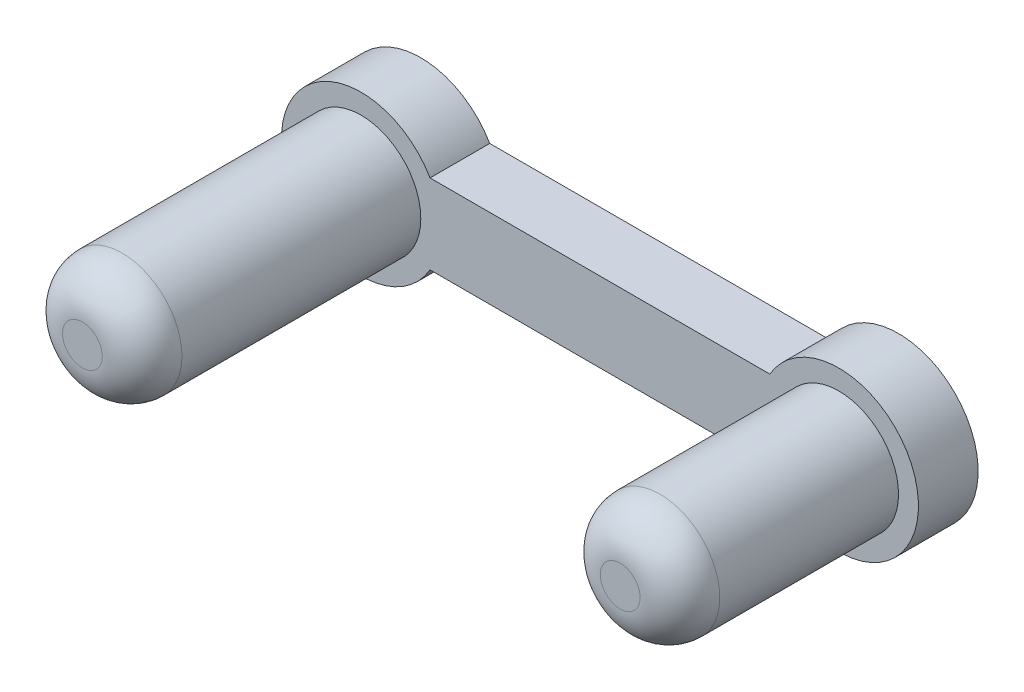
SolidWorks part; units mm, degrees
material "Custom Plastic"
ref_plane "Front Plane" through (0, 0, 0) normal (0, 0, 1) x (1, 0, 0)
ref_plane "Top Plane" through (0, 0, 0) normal (0, 1, 0) x (1, 0, 0)
ref_plane "Right Plane" through (0, 0, 0) normal (1, 0, 0) x (0, 0, -1)
sketch "Sketch1" plane through (0, 0, 0) normal (0, 0, 1) x (1, 0, 0)
  line L1 (0, 0) -> (150, 0)
  line L2 (0, 0) -> (0, -90)
  line L3 (0, -90) -> (150, -90)
  line L4 (150, 0) -> (150, -90)
  dimension "D1" = 150
  dimension "D2" = 90
extrude "Boss-Extrude1" add sketch "Sketch1" along normal blind 70
shell "Shell4" thickness 5 removed face at (75, -45, 70)
sketch "Sketch2" plane through (0, 0, 5) normal (0, 0, 1) x (1, 0, 0)
  line L0 (45, -45) -> (0, -45) construction
  line L2 (150, -90) -> (150, 0) construction
  line L3 (0, 0) -> (0, -90) construction
  line L4 (105, -45) -> (150, -45) construction
  circle A0 centre (45, -45) radius 20
  circle A1 centre (105, -45) radius 20
  dimension "D1" = 40
  dimension "D2" = 60
extrude "Boss-Extrude2" add sketch "Sketch2" along normal blind 2.5 contours A0 | A0 | A1 | A1 | A0 | A1 region at (45, -45, 5) region at (105, -45, 5)
sketch "Sketch3" plane through (0, 0, 7.5) normal (0, 0, 1) x (1, 0, 0)
  circle A0 centre (105, -45) radius 20 construction
  circle A1 centre (45, -45) radius 20 construction
  circle A2 centre (105, -45) radius 20
  circle A3 centre (45, -45) radius 20
  circle A4 centre (45, -45) radius 7.5
  circle A5 centre (105, -45) radius 7.5
  dimension "D1" = 15
extrude "Boss-Extrude3" add sketch "Sketch3" along normal blind 35 contours A4 | A5 | A4 | A5 region at (45, -45, 7.5) region at (105, -45, 7.5)
sketch "Sketch4" plane through (0, -90, 0) normal (0, -1, 0) x (1, 0, 0)
  line L0 (85, 49.9544) -> (85, 74.6585)
  line L2 (150, 70) -> (150, 34.9544)
  line L3 (150, 34.9544) -> (85, 34.9544)
  line L4 (0, 0) -> (150, 0)
  line L5 (150, 0) -> (150, 70)
  line L6 (150, 70) -> (0, 70)
  line L7 (0, 70) -> (0, 0)
  line L8 (0, 0) -> (150, 0)
  line L9 (150, 0) -> (150, 70)
  line L10 (150, 70) -> (0, 70)
  line L11 (0, 70) -> (0, 0)
  line L12 (85, 49.9544) -> (85, 34.9544)
  line L13 (85, 74.6585) -> (150, 74.6585)
  line L14 (150, 74.6585) -> (150, 70)
  line M6 (150, 0) -> (150, 70)
  line M7 (150, 70) -> (0, 70)
  dimension "D2" = 15
  dimension "D3" = 65
  dimension "D1" = 0
ref_plane "Plane2" through (0, -100, 0) normal (0, 1, 0) x (1, 0, 0)
extrude "Cut-Extrude1" cut sketch "Sketch4" against normal through all contours L12 L3 M7 M6 | L14 L13 L0 M7 region at (117.5, -90, 52.4772) region at (117.5, -90, 72.3292)
sketch "Sketch6" plane through (0, 0, 34.9544) normal (0, 0, 1) x (1, 0, 0)
  line L1 (95, -87.5) -> (90, -87.5)
  line L13 (115, -87.5) -> (120, -87.5)
  line L16 (150, 0) -> (85, 0) construction
  line L17 (90, 0) -> (120, 0)
  line L24 (90, 0) -> (90, -90)
  line L26 (120, 0) -> (120, -90)
  line L27 (150, -90) -> (85, -90) construction
  line L28 (90, -90) -> (120, -90)
  line L29 (95, -1) -> (98, -1)
  line L30 (95, -1) -> (95, -4)
  line L31 (95, -4) -> (98, -4)
  line L32 (98, -1) -> (98, -4)
  line L33 (112, -1) -> (115, -1)
  line L34 (112, -1) -> (112, -4)
  line L35 (112, -4) -> (115, -4)
  line L36 (115, -1) -> (115, -4)
  line L45 (96.5, -1) -> (96.5, 0)
  line L46 (85, -90) -> (90, -90)
  line L47 (95, -86) -> (98, -86)
  line L48 (95, -86) -> (95, -89)
  line L49 (95, -89) -> (98, -89)
  line L50 (98, -86) -> (98, -89)
  line L51 (112, -86) -> (115, -86)
  line L52 (112, -86) -> (112, -89)
  line L53 (112, -89) -> (115, -89)
  line L54 (115, -86) -> (115, -89)
  line L55 (96.5, -4) -> (96.5, -5)
  line L56 (145, -5) -> (85, -5) construction
  line L57 (95, -2.5) -> (90, -2.5)
  line L58 (115, -2.5) -> (120, -2.5)
  line L59 (96.5, -86) -> (96.5, -85)
  line L60 (5, -85) -> (145, -85) construction
  line L61 (96.5, -89) -> (96.5, -90)
  line L62 (120, -45) -> (125, -45)
  line L63 (90, -45) -> (85, -45)
  circle A0 centre (105, -45) radius 20 construction
  circle A1 centre (105, -45) radius 20 construction
  dimension "D1" = 3
  dimension "D3" = 30
  dimension "D4" = 5
extrude "Cut-Extrude3" cut sketch "Sketch6" against normal blind 40 contours L50 L47 L48 L49 | L54 L51 L52 L53 | L32 L29 L30 L31 | L36 L33 L34 L35 region at (113.5, -87.5, 34.9544) region at (113.5, -2.5, 34.9544) region at (96.5, -87.5, 34.9544) region at (96.5, -2.5, 34.9544)
fillet "Fillet4" radius 5 12 edges at (150, 0, 17.4772) (145, -5, 19.9772) (145, -85, 19.9772) (5, -85, 37.5) (0, 0, 35) (5, -5, 37.5) (0, -90, 35) (150, -90, 17.4772) (85, -2.5, 34.9544) (85, -2.5, 70) (85, -87.5, 70) (85, -87.5, 34.9544)
sketch "Sketch8" plane through (0, 0, 5) normal (0, 0, 1) x (1, 0, 0)
  line L0 (75, -5) -> (75, -85) construction
  line L1 (140, -5) -> (10, -5) construction
  line L2 (10, -85) -> (140, -85) construction
  line L3 (5, -45) -> (145, -45) construction
  line L4 (5, -10) -> (5, -80) construction
  line L5 (145, -80) -> (145, -10) construction
  circle A0 centre (45, -45) radius 30
  circle A1 centre (105, -45) radius 30
  point P16 (0, 0)
  dimension "D1" = 60
fillet "Fillet5" radius 5 2 edges at (112.5, -45, 34.9544) (52.5, -45, 42.5)
sketch "Sketch10" plane through (0, 0, 70) normal (0, 0, 1) x (1, 0, 0)
  line L0 (5, -90) -> (80, -90) construction
  line L5 (75, -90) -> (0, -90)
  line L6 (75, -90) -> (75, 0)
  line L7 (75, 0) -> (0, 0)
  line L8 (0, -90) -> (0, 0)
  line L9 (37.5, -90) -> (37.5, 0) construction
  line L14 (1, -43.5) -> (4, -43.5)
  line L15 (1, -43.5) -> (1, -46.5)
  line L16 (1, -46.5) -> (4, -46.5)
  line L17 (4, -43.5) -> (4, -46.5)
  line L18 (36, -86) -> (39, -86)
  line L19 (36, -86) -> (36, -89)
  line L20 (36, -89) -> (39, -89)
  line L21 (39, -86) -> (39, -89)
  line L22 (36, -1) -> (39, -1)
  line L23 (36, -1) -> (36, -4)
  line L24 (36, -4) -> (39, -4)
  line L25 (39, -1) -> (39, -4)
  line L26 (37.5, -45) -> (0, -45) construction
  line L27 (4, -46.5) -> (1, -43.5) construction
  line L28 (1, -45) -> (0, -45)
  line L29 (4, -45) -> (5, -45)
  line L30 (37.5, -86) -> (37.5, -85)
  line L32 (10, -85) -> (140, -85) construction
  line L33 (37.5, -89) -> (37.5, -90)
  line L34 (39, -89) -> (36, -86) construction
  line L35 (37.5, -1) -> (37.5, 0)
  line L36 (37.5, -4) -> (37.5, -5)
  line L37 (140, -5) -> (10, -5) construction
  line L38 (36, -1) -> (39, -4) construction
  line L39 (37.5, -1) -> (37.5, 0)
  line L40 (37.5, -4) -> (37.5, -5)
  circle A0 centre (45, -45) radius 30 construction
  point P23 (2.5, -45)
  point P34 (37.5, -87.5)
  point P40 (37.5, -2.5)
  dimension "D1" = 3
extrude "Cut-Extrude4" cut sketch "Sketch10" against normal blind 40 contours L17 L14 L15 L16 | L21 L18 L19 L20 | L25 L22 L23 L24 region at (37.5, -2.5, 70) region at (2.5, -45, 70) region at (37.5, -87.5, 70)
sketch "Sketch11" plane through (0, 0, 5) normal (0, 0, 1) x (1, 0, 0)
  line L0 (90, 0) -> (85, 0) construction
  line L1 (85, 0) -> (85, -5) construction
  line L2 (85, -5) -> (90, -5) construction
  line L3 (80, -5) -> (85, -5) construction
  line L4 (85, -5) -> (85, 0) construction
  line L5 (85, 0) -> (80, 0) construction
  line L6 (150, -85) -> (150, -5) construction
  line L7 (145, 0) -> (90, 0) construction
  line L8 (90, -5) -> (140, -5) construction
  line L9 (145, -10) -> (145, -80) construction
  line L10 (140, -85) -> (90, -85) construction
  line L11 (90, -90) -> (145, -90) construction
  line L12 (90, -85) -> (85, -85) construction
  line L13 (85, -85) -> (85, -90) construction
  line L14 (85, -90) -> (90, -90) construction
  line L15 (80, -90) -> (85, -90) construction
  line L16 (85, -90) -> (85, -85) construction
  line L17 (85, -85) -> (80, -85) construction
  line L18 (39, -89) -> (39, -86) construction
  line L19 (39, -86) -> (36, -86) construction
  line L20 (36, -86) -> (36, -89) construction
  line L21 (36, -89) -> (39, -89) construction
  line L22 (4, -46.5) -> (4, -43.5) construction
  line L23 (4, -43.5) -> (1, -43.5) construction
  line L24 (1, -43.5) -> (1, -46.5) construction
  line L25 (1, -46.5) -> (4, -46.5) construction
  line L26 (39, -4) -> (39, -1) construction
  line L27 (39, -1) -> (36, -1) construction
  line L28 (36, -1) -> (36, -4) construction
  line L29 (36, -4) -> (39, -4) construction
  line L30 (10, -5) -> (80, -5) construction
  line L31 (80, 0) -> (5, 0) construction
  line L32 (0, -5) -> (0, -85) construction
  line L33 (5, -90) -> (80, -90) construction
  line L34 (80, -85) -> (10, -85) construction
  line L35 (5, -80) -> (5, -10) construction
  line L36 (145, -80) -> (145, -10) construction
  line L37 (140, -5) -> (10, -5) construction
  line L38 (5, -10) -> (5, -80) construction
  line L39 (10, -85) -> (140, -85) construction
  line L40 (90, 0) -> (85, 0)
  line L41 (85, 0) -> (85, -5)
  line L42 (85, -5) -> (90, -5)
  line L43 (80, -5) -> (85, -5)
  line L44 (85, -5) -> (85, 0)
  line L45 (85, 0) -> (80, 0)
  line L46 (150, -85) -> (150, -5)
  line L47 (145, 0) -> (90, 0)
  line L48 (90, -5) -> (140, -5)
  line L49 (145, -10) -> (145, -80)
  line L50 (140, -85) -> (90, -85)
  line L51 (90, -90) -> (145, -90)
  line L52 (90, -85) -> (85, -85)
  line L53 (85, -85) -> (85, -90)
  line L54 (85, -90) -> (90, -90)
  line L55 (80, -90) -> (85, -90)
  line L56 (85, -90) -> (85, -85)
  line L57 (85, -85) -> (80, -85)
  line L58 (39, -89) -> (39, -86)
  line L59 (39, -86) -> (36, -86)
  line L60 (36, -86) -> (36, -89)
  line L61 (36, -89) -> (39, -89)
  line L62 (4, -46.5) -> (4, -43.5)
  line L63 (4, -43.5) -> (1, -43.5)
  line L64 (1, -43.5) -> (1, -46.5)
  line L65 (1, -46.5) -> (4, -46.5)
  line L66 (39, -4) -> (39, -1)
  line L67 (39, -1) -> (36, -1)
  line L68 (36, -1) -> (36, -4)
  line L69 (36, -4) -> (39, -4)
  line L70 (10, -5) -> (80, -5)
  line L71 (80, 0) -> (5, 0)
  line L72 (0, -5) -> (0, -85)
  line L73 (5, -90) -> (80, -90)
  line L74 (80, -85) -> (10, -85)
  line L75 (5, -80) -> (5, -10)
  line L76 (145, -80) -> (145, -10)
  line L77 (140, -5) -> (10, -5)
  line L78 (5, -10) -> (5, -80)
  line L79 (10, -85) -> (140, -85)
  arc A0 (150, -5) -> (145, 0) centre (145, -5) ccw construction
  arc A1 (145, -10) -> (140, -5) centre (140, -10) ccw construction
  arc A2 (140, -85) -> (145, -80) centre (140, -80) ccw construction
  arc A3 (145, -90) -> (150, -85) centre (145, -85) ccw construction
  arc A4 (5, 0) -> (0, -5) centre (5, -5) ccw construction
  arc A5 (0, -85) -> (5, -90) centre (5, -85) ccw construction
  arc A6 (5, -80) -> (10, -85) centre (10, -80) ccw construction
  arc A7 (10, -5) -> (5, -10) centre (10, -10) ccw construction
  arc A8 (145, -10) -> (140, -5) centre (140, -10) ccw construction
  arc A9 (10, -5) -> (5, -10) centre (10, -10) ccw construction
  arc A10 (5, -80) -> (10, -85) centre (10, -80) ccw construction
  arc A11 (140, -85) -> (145, -80) centre (140, -80) ccw construction
  arc A12 (150, -5) -> (145, 0) centre (145, -5) ccw
  arc A13 (145, -10) -> (140, -5) centre (140, -10) ccw
  arc A14 (140, -85) -> (145, -80) centre (140, -80) ccw
  arc A15 (145, -90) -> (150, -85) centre (145, -85) ccw
  arc A16 (5, 0) -> (0, -5) centre (5, -5) ccw
  arc A17 (0, -85) -> (5, -90) centre (5, -85) ccw
  arc A18 (5, -80) -> (10, -85) centre (10, -80) ccw
  arc A19 (10, -5) -> (5, -10) centre (10, -10) ccw
  arc A20 (145, -10) -> (140, -5) centre (140, -10) ccw
  arc A21 (10, -5) -> (5, -10) centre (10, -10) ccw
  arc A22 (5, -80) -> (10, -85) centre (10, -80) ccw
  arc A23 (140, -85) -> (145, -80) centre (140, -80) ccw
  circle M1 centre (45, -45) radius 20
  circle M2 centre (105, -45) radius 20
  line M3 (145, -80) -> (145, -10)
  arc M4 (145, -10) -> (140, -5) centre (140, -10) ccw
  line M5 (140, -5) -> (10, -5)
  arc M6 (10, -5) -> (5, -10) centre (10, -10) ccw
  line M7 (5, -10) -> (5, -80)
  arc M8 (5, -80) -> (10, -85) centre (10, -80) ccw
  line M9 (10, -85) -> (140, -85)
  arc M10 (140, -85) -> (145, -80) centre (140, -80) ccw
extrude "Cut-Extrude5" cut sketch "Sketch11" against normal through all both and the other way through all contours L72 A17 L73 L55 L53 L41 L45 L71 A16 L61 L60 L59 L58 L65 L64 L63 L62 L69 L68 L67 L66 M9 M8 M7 M6 M5 | M10 M3 M4 M5 M6 M7 M8 M9 M2 M1 | L51 A15 L46 A12 L47 L40 L41 L53 L54 M5 M4 M3 M10 M9 | L64 L65 L62 L63 | L66 L67 L68 L69 | L61 L58 L59 L60 region at (117.5, -1.1102, 5) region at (83.7621, -2.5, 5) region at (75, -45, 5) region at (2.5, -45, 5)
sketch "Sketch12" plane through (0, 0, 7.5) normal (0, 0, 1) x (1, 0, 0)
  line L0 (5, -45) -> (145, -45) construction
  line L1 (60, -40) -> (90, -40)
  line L2 (60, -40) -> (60, -50)
  line L3 (60, -50) -> (90, -50)
  line L4 (90, -40) -> (90, -50)
  circle A0 centre (45, -45) radius 30 construction
  point P8 (60, -45)
  dimension "D1" = 10
  dimension "D2" = 30
  dimension "D3" = 15
extrude "Boss-Extrude4" add sketch "Sketch12" against normal up to surface (7.5 mm away) up to face at (65, -45, 0)
sketch "Sketch13" plane through (0, 0, 7.5) normal (0, 0, 1) x (1, 0, 0)
  line L0 (64.3649, -50) -> (53.6603, -50)
  line L1 (64.3649, -40) -> (53.6603, -40)
  line L2 (64.3649, -50) -> (85.6351, -50)
  line L3 (85.6351, -40) -> (64.3649, -40)
  line L4 (64.3649, -50) -> (85.6351, -50)
  line L5 (85.6351, -40) -> (64.3649, -40)
  line L6 (85.6351, -40) -> (96.3397, -40)
  line L7 (96.3397, -40) -> (96.3397, -50)
  line L8 (96.3397, -50) -> (85.6351, -50)
  circle A0 centre (45, -45) radius 10
  circle A1 centre (105, -45) radius 10
  arc A2 (85.6351, -50) -> (85.6351, -40) centre (105, -45) ccw
  arc A3 (64.3649, -40) -> (64.3649, -50) centre (45, -45) ccw
  arc A4 (85.6351, -50) -> (85.6351, -40) centre (105, -45) ccw
  arc A5 (64.3649, -40) -> (64.3649, -50) centre (45, -45) ccw
  circle A6 centre (45, -45) radius 20
  circle A7 centre (105, -45) radius 20
  arc M8 (85.6351, -50) -> (85.6351, -40) centre (105, -45) ccw
  arc M10 (64.3649, -40) -> (64.3649, -50) centre (45, -45) ccw
  dimension "D2" = 20
  dimension "D3" = 20
  dimension "D1" = 0
extrude "Cut-Extrude8" cut sketch "Sketch13" against normal through all both and the other way through all contours A0 L1 L0 M10 | A1 L8 L6 M8 region at (25.5612, -45, 7.5) region at (90.9874, -50.5612, 7.5)
